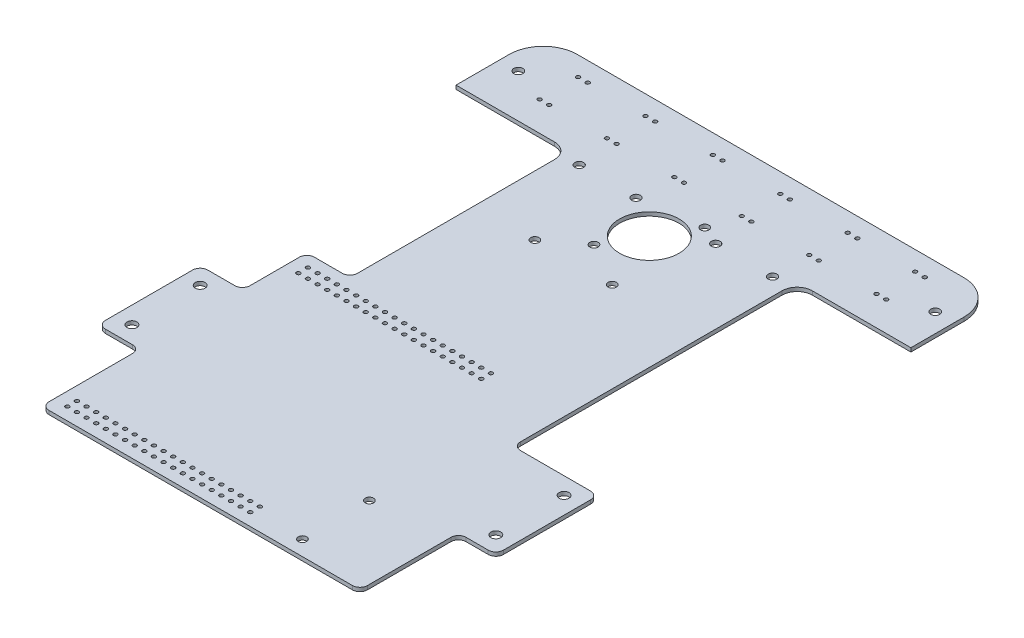
SolidWorks part; units mm, degrees
material "Thornel VCB-20 Carbon Cloth"
ref_plane "Front" through (0, 0, 0) normal (0, 0, 1) x (1, 0, 0)
ref_plane "Top" through (0, 0, 0) normal (0, 1, 0) x (1, 0, 0)
ref_plane "Right" through (0, 0, 0) normal (1, 0, 0) x (0, 0, -1)
ref_axis "X" through (-80.9, 0, 0) along (1, 0, 0)
ref_axis "Y" through (0, -50, 0) along (0, 1, 0)
ref_axis "Z" through (0, 0, -80.9) along (0, 0, 1)
sketch "Sketch1" plane through (0, 0, 0) normal (0, 1, 0) x (1, 0, 0)
  line L0 (-52.5, -125) -> (-41.35, -125)
  line L1 (-52.5, -125) -> (-52.5, -98)
  line L2 (-52.5, -98) -> (-41.35, -98)
  line L3 (-30, -81) -> (-30, -23)
  line L4 (-30, -23) -> (-60, -23)
  line L5 (-60, -23) -> (-60, 0)
  line L6 (-60, 0) -> (60, 0)
  line L7 (60, 0) -> (60, -23)
  line L8 (60, -23) -> (30, -23)
  line L9 (30, -23) -> (30, -98)
  line L10 (30, -98) -> (52.5, -98)
  line L11 (52.5, -98) -> (52.5, -125)
  line L12 (0, -162) -> (0, 0) construction
  line L13 (-41.35, -125) -> (-41.35, -151)
  line L14 (-41.35, -151) -> (42.65, -151)
  line L15 (42.65, -151) -> (42.65, -125)
  line L16 (42.65, -125) -> (52.5, -125)
  line L18 (-41.35, -98) -> (-41.35, -81)
  line L19 (-41.35, -81) -> (-30, -81)
  dimension "D1" = 105
  dimension "D2" = 60
  dimension "D3" = 27
  dimension "D4" = 90
  dimension "D5" = 23
  dimension "D6" = 120
  dimension "D7" = 125
  dimension "D8" = 41.35
  dimension "D9" = 26
  dimension "D10" = 42.65
  dimension "D11" = 17
extrude "Boss-Extrude1" add sketch "Sketch1" along normal mid plane 1
hole_wizard "M2 Clearance Hole1" positions "Sketch2" profile "Sketch3" hole size "M2" standard "ANSI Metric" end condition up to next
sketch "Sketch2" plane through (0, 0.5, 0) normal (0, 1, 0) x (1, 0, 0)
  line L0 (-48, -120.5) -> (48, -120.5) construction
  line L2 (-52.5, -125) -> (-41.35, -125) construction
  line L3 (-52.5, -98) -> (-52.5, -125) construction
  line L4 (52.5, -125) -> (52.5, -98) construction
  line L5 (-48, -102.5) -> (-48, -120.5) construction
  line L8 (48, -102.5) -> (48, -120.5) construction
  point P0 (-48, -120.5)
  point P2 (48, -120.5)
  point P15 (-48, -102.5)
  point P17 (48, -102.5)
  dimension "D1" = 4.5
  dimension "D2" = 4.5
  dimension "D3" = 4.5
  dimension "D4" = 18
sketch "Sketch3" plane through (-48, 0.5, 120.5) normal (1, 0, 0) x (0, 0, 1)
  line L0 (0, 0) -> (0, 1)
  line L1 (0, 1) -> (1.3, 1)
  line L2 (1.3, 1) -> (1.3, 0)
  line L5 (1.3, 0) -> (0, 0)
  line L11 (0, -6.35) -> (0, 107.95) construction
  dimension "Thru Hole Dia." = 2.6
  dimension "Thru Hole Depth" = 1
fillet "Fillet1" radius 2 7 edges at (-52.5, 0, 125) (52.5, 0, 98) (-52.5, 0, 98) (-41.35, 0, 151) (42.65, 0, 151) (52.5, 0, 125) (-41.35, 0, 81)
fillet "Fillet2" radius 9 2 edges at (60, 0, 0) (-60, 0, 0)
hole_wizard "M2 Clearance Hole2" positions "Sketch7" profile "Sketch8" hole size "M2" standard "ANSI Metric" end condition up to next
sketch "Sketch7" plane through (0, 0.5, 0) normal (0, 1, 0) x (1, 0, 0)
  line L0 (-55, -11.57) -> (55, -11.57) construction
  line L2 (0, 0) -> (0, -11.57) construction
  line L3 (51, 0) -> (-51, 0) construction
  line L5 (-60, -23) -> (-30, -23) construction
  point P0 (-55, -11.57)
  point P2 (55, -11.57)
  dimension "D1" = 110
  dimension "D2" = 11.43
sketch "Sketch8" plane through (-55, 0.5, 11.57) normal (1, 0, 0) x (0, 0, 1)
  line L0 (0, 0) -> (0, 1)
  line L1 (0, 1) -> (1.2, 1)
  line L2 (1.2, 1) -> (1.2, 0)
  line L5 (1.2, 0) -> (0, 0)
  line L11 (0, -6.35) -> (0, 107.95) construction
  dimension "Thru Hole Dia." = 2.4
  dimension "Thru Hole Depth" = 1
fillet "Fillet4" radius 2 5 edges at (30, 0, 98) (42.65, 0, 125) (-41.35, 0, 125) (-30, 0, 81) (-41.35, 0, 98)
fillet "Fillet5" radius 4 2 edges at (30, 0, 23) (-30, 0, 23)
sketch "Sketch13" plane through (0, 0.5, 0) normal (0, 1, 0) x (1, 0, 0)
  line L0 (-38, -106) -> (-38, -117) construction
  line L1 (-35, -106) -> (-35, -117)
  line L3 (38, -106) -> (38, -117) construction
  line L5 (35, -106) -> (35, -117)
  line L6 (-38, -111.5) -> (38, -111.5) construction
  line L7 (0, -111.5) -> (0, 0) construction
  line L8 (51, 0) -> (-51, 0) construction
  line L11 (-48, -102.5) -> (-48, -120.5) construction
  line L12 (-48, -111.5) -> (-38, -111.5) construction
  line L13 (-38, -103) -> (-45.5, -103)
  line L14 (-38, -120) -> (-45.5, -120)
  line L15 (38, -103) -> (45.5, -103)
  line L16 (38, -120) -> (45.5, -120)
  line L17 (48.5, -106) -> (48.5, -117)
  line L18 (-48.5, -106) -> (-48.5, -117)
  line L19 (-35, -111.5) -> (-48.5, -111.5) construction
  line L20 (35, -111.5) -> (48.5, -111.5) construction
  arc A0 (-35, -106) -> (-38, -103) centre (-38, -106) ccw
  arc A1 (-38, -120) -> (-35, -117) centre (-38, -117) ccw
  arc A2 (38, -103) -> (35, -106) centre (38, -106) ccw
  arc A3 (35, -117) -> (38, -120) centre (38, -117) ccw
  circle A4 centre (-48, -102.5) radius 1.3 construction
  arc A5 (45.5, -103) -> (48.5, -106) centre (45.5, -106) cw
  arc A6 (48.5, -117) -> (45.5, -120) centre (45.5, -117) cw
  arc A7 (-45.5, -103) -> (-48.5, -106) centre (-45.5, -106) ccw
  arc A8 (-48.5, -117) -> (-45.5, -120) centre (-45.5, -117) ccw
  point P2 (-38, -111.5)
  point P8 (38, -111.5)
  dimension "D5" = 3.5
  dimension "D1" = 17
  dimension "D2" = 13.5
  dimension "D3" = 70
extrude "Cut-Extrude4" [suppressed] cut sketch "Sketch13" against normal through all
hole_wizard "M2 Clearance Hole3" positions "Sketch14" profile "Sketch15" hole size "M2" standard "ANSI Metric" end condition up to next
sketch "Sketch14" plane through (0, 0.5, 0) normal (0, 1, 0) x (1, 0, 0)
  line L2 (5.35, -22.7335) -> (-5.35, -41.2665) construction
  line L3 (0, 0) -> (0, -32) construction
  line L4 (51, 0) -> (-51, 0) construction
  point P0 (5.35, -22.7335)
  point P2 (-5.35, -41.2665)
  dimension "D1" = 21.4
  dimension "D2" = 32
  dimension "D3" = 30
sketch "Sketch15" plane through (5.35, 0.5, 22.7335) normal (1, 0, 0) x (0, 0, 1)
  line L0 (0, 0) -> (0, 1)
  line L1 (0, 1) -> (1.1, 1)
  line L2 (1.1, 1) -> (1.1, 0)
  line L5 (1.1, 0) -> (0, 0)
  line L11 (0, -6.35) -> (0, 107.95) construction
  dimension "Thru Hole Dia." = 2.2
  dimension "Thru Hole Depth" = 1
sketch "Sketch17" plane through (0, 0.5, 0) normal (0, 1, 0) x (1, 0, 0)
  line L0 (-25.5, -25) -> (-10.5, -25) construction
  line L1 (-10.5, -25) -> (10.5, -25) construction
  line L2 (10.5, -25) -> (25.5, -25) construction
  line L4 (0, -25) -> (0, 0) construction
  line L5 (-18, -25) -> (-18, -29.652) construction
  line L7 (51, 0) -> (-51, 0) construction
  line L8 (18, -25) -> (18, -28.4507) construction
  circle A8 centre (25.5, -25) radius 1.15
  circle A9 centre (10.5, -25) radius 1.15
  circle A10 centre (-10.5, -25) radius 1.15
  circle A11 centre (-25.5, -25) radius 1.15
  dimension "D7" = 2.3
  dimension "D1" = 15
  dimension "D2" = 36
  dimension "D4" = 25
extrude "Cut-Extrude6" cut sketch "Sketch17" against normal through all
sketch "Sketch18" plane through (0, 0.5, 0) normal (0, 1, 0) x (1, 0, 0)
  line L0 (5.35, -22.7335) -> (-5.35, -41.2665) construction
  circle A0 centre (0, -32) radius 7.85
  circle A6 centre (5.35, -22.7335) radius 1.1 construction
  circle A8 centre (-5.35, -41.2665) radius 1.1 construction
  dimension "D3" = 15.7
extrude "Cut-Extrude7" cut sketch "Sketch18" against normal up to next
hole_wizard "M2 Clearance Hole4" positions "Sketch19" profile "Sketch20" hole size "M2" standard "ANSI Metric" end condition up to next
sketch "Sketch19" plane through (0, 0.5, 0) normal (0, 1, 0) x (1, 0, 0)
  line L0 (-14.21, -48) -> (6.21, -48) construction
  line L2 (0, 0) -> (0, -48) construction
  line L3 (51, 0) -> (-51, 0) construction
  point P0 (-14.21, -48)
  point P2 (6.21, -48)
  dimension "D1" = 20.42
  dimension "D2" = 6.21
  dimension "D3" = 48
sketch "Sketch20" plane through (-14.21, 0.5, 48) normal (1, 0, 0) x (0, 0, 1)
  line L0 (0, 0) -> (0, 1)
  line L1 (0, 1) -> (1.1, 1)
  line L2 (1.1, 1) -> (1.1, 0)
  line L5 (1.1, 0) -> (0, 0)
  line L11 (0, -6.35) -> (0, 107.95) construction
  dimension "Thru Hole Dia." = 2.2
  dimension "Thru Hole Depth" = 1
sketch "Sketch21" plane through (0, 0.5, 0) normal (0, 1, 0) x (1, 0, 0)
  line L0 (-37.826, -86.7798) -> (-37.826, -147.73) construction
  line L4 (-39.35, -151) -> (40.65, -151) construction
  line L5 (-41.35, -127) -> (-41.35, -149) construction
  circle A0 centre (-37.826, -147.73) radius 0.51
  circle A2 centre (-37.826, -86.7798) radius 0.51
  dimension "D2" = 1.02
  dimension "D3" = 3.524
  dimension "D4" = 3.27
  dimension "D1" = 60.9502
extrude "Cut-Extrude8" cut sketch "Sketch21" against normal up to next
pattern_linear "LPattern1" count 2 spacing 2.54 along (0, 0, -1) count 20 spacing 2.54 along (1, 0, 0) of "Cut-Extrude8"
sketch "Sketch22" plane through (0, 0.5, 0) normal (0, 1, 0) x (1, 0, 0)
  line L0 (-45.72, -5.08) -> (-43.18, -5.08) construction
  line L1 (51, 0) -> (-51, 0) construction
  line L2 (-44.45, -5.08) -> (-44.45, 0) construction
  circle A0 centre (-45.72, -5.08) radius 0.51
  circle A1 centre (-43.18, -5.08) radius 0.51
  point P8 (0, 0)
  dimension "D2" = 1.02
  dimension "D1" = 2.54
  dimension "D3" = 5.08
  dimension "D4" = 44.45
extrude "Cut-Extrude9" cut sketch "Sketch22" against normal up to next
pattern_linear "LPattern2" count 2 spacing 10.16 along (0, 0, 1) count 6 spacing 17.78 along (1, 0, 0) of "Cut-Extrude9"
sketch "Sketch23" plane through (0, 0.5, 0) normal (0, 1, 0) x (1, 0, 0)
  line L0 (42.65, -149) -> (42.65, -127) construction
  line L1 (-39.35, -151) -> (40.65, -151) construction
  circle A0 centre (23.48, -147) radius 1.1
  circle A1 centre (23.48, -129.35) radius 1.1
  dimension "D1" = 2.2
  dimension "D2" = 17.65
  dimension "D3" = 19.17
  dimension "D4" = 4
extrude "Cut-Extrude10" cut sketch "Sketch23" against normal through all
equation "\"dd\"=4"
